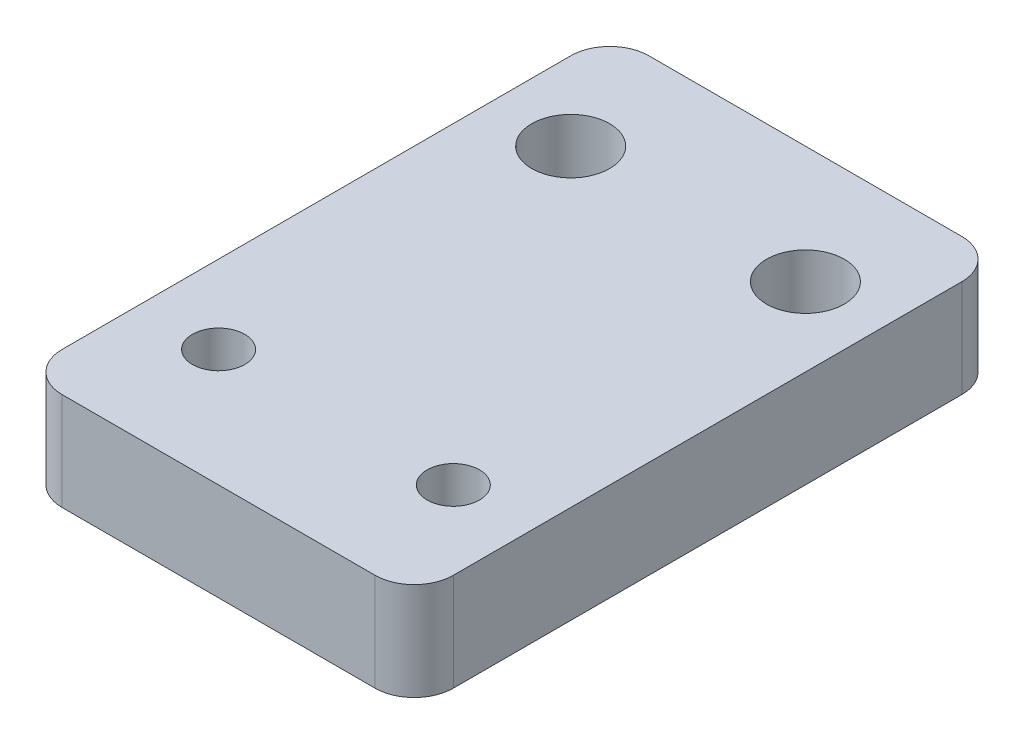
SolidWorks part; units mm, degrees
ref_plane "Front Plane" through (0, 0, 0) normal (0, 0, 1) x (1, 0, 0)
ref_plane "Top Plane" through (0, 0, 0) normal (0, 1, 0) x (1, 0, 0)
ref_plane "Right Plane" through (0, 0, 0) normal (1, 0, 0) x (0, 0, -1)
sketch "Sketch1" plane through (0, 0, 0) normal (0, 1, 0) x (1, 0, 0)
  line L0 (0, 0) -> (0, -11.43) construction
  line L5 (-12.7, -19.05) -> (12.7, -19.05)
  line L6 (-12.7, -19.05) -> (-12.7, 19.05)
  line L12 (-12.7, 19.05) -> (12.7, 19.05)
  line L13 (12.7, -19.05) -> (12.7, 19.05)
  line L14 (-12.7, -19.05) -> (12.7, 19.05) construction
  line L15 (-12.7, 19.05) -> (12.7, -19.05) construction
  line L16 (-7.62, -11.43) -> (7.62, -11.43) construction
  line L17 (0, 0) -> (0, 11.43) construction
  line L18 (-7.62, 11.43) -> (7.62, 11.43) construction
  circle A2 centre (-7.62, -11.43) radius 1.7
  circle A3 centre (7.62, -11.43) radius 1.7
  circle A4 centre (-7.62, 11.43) radius 2.5273
  circle A5 centre (7.62, 11.43) radius 2.5273
  point P0 (0, 0)
  point P10 (0, -11.43)
  point P16 (0, 11.43)
  dimension "D3" = 7.62
  dimension "D4" = 5.0546
  dimension "D5" = 25.4
  dimension "D8" = 3.4
  dimension "D1" = 38.1
  dimension "D2" = 15.24
  dimension "D6" = 7.62
  dimension "D7" = 15.24
extrude "Boss-Extrude1" add sketch "Sketch1" along normal blind 6.35
fillet "Fillet1" radius 2.54 4 edges at (12.7, 3.175, 19.05) (-12.7, 3.175, -19.05) (12.7, 3.175, -19.05) (-12.7, 3.175, 19.05)
